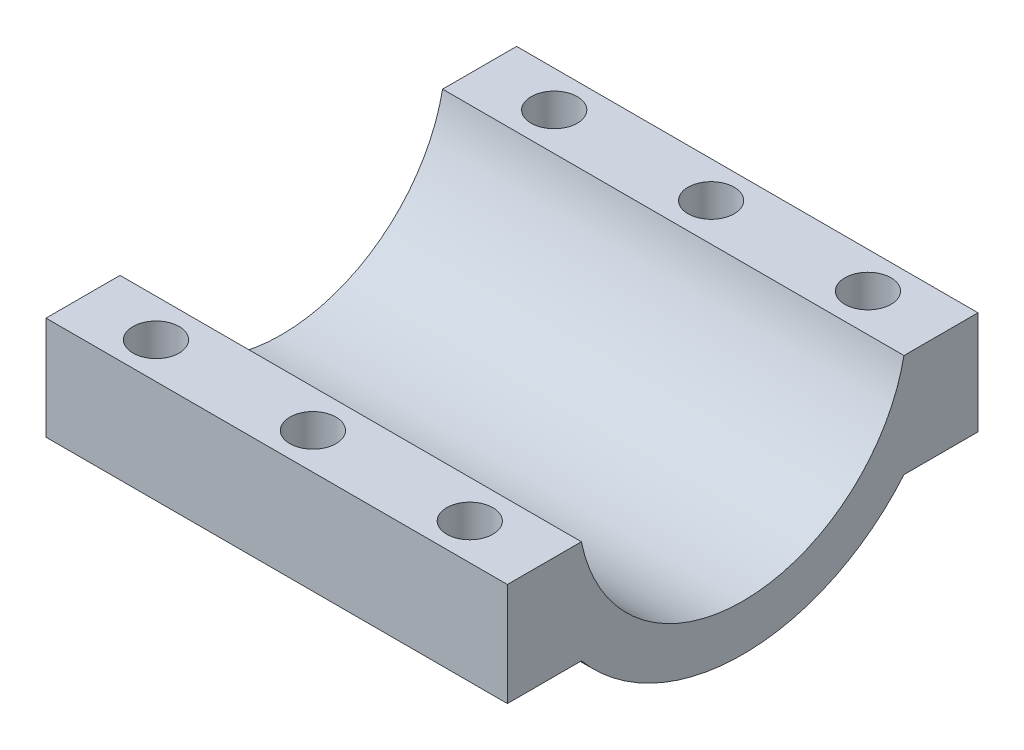
SolidWorks part; units mm, degrees
ref_plane "Front Plane" through (0, 0, 0) normal (0, 0, 1) x (1, 0, 0)
ref_plane "Top Plane" through (0, 0, 0) normal (0, 1, 0) x (1, 0, 0)
ref_plane "Right Plane" through (0, 0, 0) normal (1, 0, 0) x (0, 0, -1)
sketch "Sketch1" plane through (0, 0, 0) normal (0, 1, 0) x (1, 0, 0)
  line L0 (-40.0608, 0) -> (47.511, 0) construction
  line L1 (-25, -25.5) -> (25, -25.5)
  line L2 (-25, -25.5) -> (-25, 25.5)
  line L3 (-25, 25.5) -> (25, 25.5)
  line L4 (25, -25.5) -> (25, 25.5)
  line L5 (-25, -25.5) -> (25, 25.5) construction
  line L6 (-25, 25.5) -> (25, -25.5) construction
  line L7 (-25, 21.575) -> (25, 21.575) construction
  line L8 (-25, 18.075) -> (25, 18.075) construction
  line L9 (-25, -21.575) -> (25, -21.575) construction
  line L10 (-25, -18.075) -> (25, -18.075) construction
  line L11 (0, -25.5) -> (0, 25.5) construction
  circle A0 centre (-17, 21.575) radius 2.5
  circle A1 centre (17, 21.575) radius 2.5
  circle A2 centre (17, -21.575) radius 2.5
  circle A3 centre (-17, -21.575) radius 2.5
  circle A4 centre (0, 21.575) radius 2.5
  circle A5 centre (0, -21.575) radius 2.5
  point P0 (0, 0)
  dimension "D3" = 5
  dimension "D4" = 5
  dimension "D9" = 5
  dimension "D10" = 5
  dimension "D1" = 50
  dimension "D2" = 51
  dimension "D5" = 8
  dimension "D6" = 8
  dimension "D7" = 18.075
  dimension "D8" = 3.5
extrude "Boss-Extrude1" add sketch "Sketch1" along normal blind 19.325
sketch "Sketch2" plane through (25, 0, 0) normal (1, 0, 0) x (0, 0, -1)
  line L0 (-25.5, 19.325) -> (25.5, 19.325) construction
  line L1 (-25.5, 19.325) -> (-17.478, 19.325) construction
  line L2 (-17.478, 19.325) -> (-17.478, 0) construction
  line L3 (-25.5, 0) -> (25.5, 0) construction
  line L4 (25.5, 19.325) -> (17.478, 19.325) construction
  line L5 (17.478, 19.325) -> (17.478, 0) construction
  line L6 (-17.478, 8.1451) -> (-25.5, 8.1451)
  line L7 (-25.5, 19.325) -> (-25.5, 0) construction
  line L11 (25.5, 19.325) -> (25.5, 0) construction
  line L12 (25.5, 8.1451) -> (17.478, 8.1451)
  line L13 (0, -12.8013) -> (0, 49.7133) construction
  line L14 (-25.5, 8.1451) -> (-25.5, -3.6218)
  line L15 (-25.5, -3.6218) -> (25.5, -3.6218)
  line L16 (25.5, -3.6218) -> (25.5, 8.1451)
  circle A0 centre (0, 22.825) radius 17.825
  arc A1 (-17.478, 8.1451) -> (17.478, 8.1451) centre (0, 22.825) ccw
  dimension "D2" = 35.65
  dimension "D1" = 3.5
  dimension "D3" = 11.7669
extrude "Cut-Extrude1" cut sketch "Sketch2" against normal through all
sketch "Sketch3" plane through (0, 8.1451, 0) normal (0, -1, 0) x (1, 0, 0)
  circle A0 centre (-17, -21.575) radius 6
  circle A1 centre (0, -21.575) radius 6
  circle A2 centre (17, -21.575) radius 6
  circle A3 centre (17, 21.575) radius 6
  circle A4 centre (0, 21.575) radius 6
  circle A5 centre (-17, 21.575) radius 6
  dimension "D1" = 12
  dimension "D2" = 12
  dimension "D3" = 12
  dimension "D4" = 12
  dimension "D5" = 12
  dimension "D6" = 12
extrude "Cut-Extrude2" cut sketch "Sketch3" along normal blind 10
